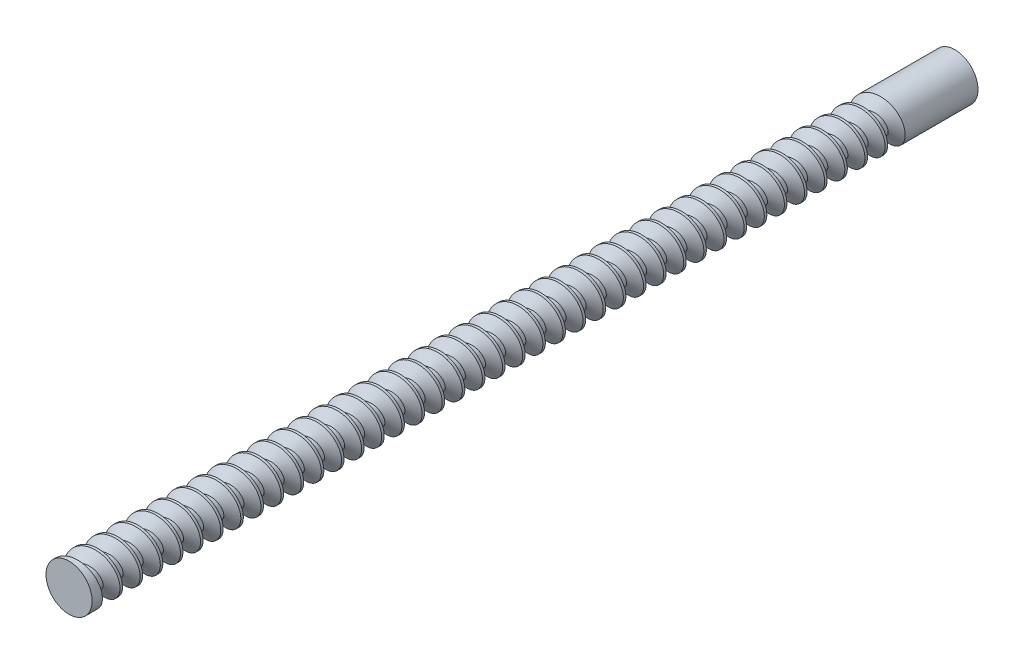
SolidWorks part; units mm, degrees
ref_plane "Top plane" through (0, 0, 0) normal (0, 0, 1) x (1, 0, 0)
ref_plane "Right plane" through (0, 0, 0) normal (0, 1, 0) x (1, 0, 0)
ref_plane "Front plane" through (0, 0, 0) normal (1, 0, 0) x (0, 0, -1)
sketch "Sketch2" plane through (0, 0, 0) normal (0, 0, 1) x (1, 0, 0)
  circle A1 centre (135.4069, -47.8082) radius 1.432
extrude "Boss-Extrude1" add sketch "Sketch2" along normal blind 55
thread "Thread1" pitch 1.25 method cut profile "Thread Profile1" start angle 0, offset 0, length 50, pitch 1.25, diameter 2.8641
ref_plane "Plane1" through (133.9749, -47.8082, 55) normal (0, -1, 0) x (-1, 0, 0)
sketch "Thread Profile1" plane through (133.9749, -47.8082, 55) normal (0, -1, 0) x (-1, 0, 0)
  line L0 (0, 0) -> (0, 1.25) construction
  line L11 (0, 0) -> (0, 1.0937)
  line L12 (0, 1.0937) -> (-0.6766, 0.7031)
  line L13 (-0.6766, 0.7031) -> (-0.6766, 0.3906)
  line L15 (-0.6766, 0.3906) -> (0, 0)
  line L17 (-0.6766, 0.5469) -> (0, 0.5469) construction
  point P2 (0, 0)
  dimension "Pitch" = 1.25
  dimension "Profile_Angle" = 60
  dimension "Profile_Land" = 0.3125
  dimension "Profile_Height" = 0.6766
